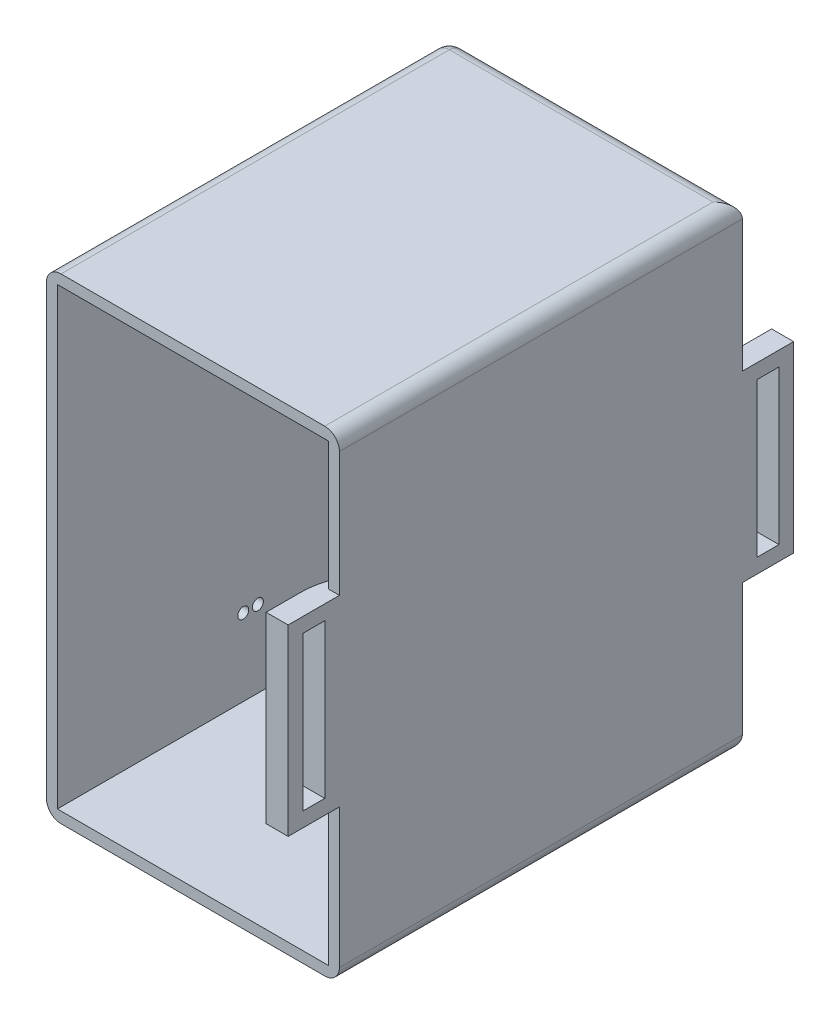
SolidWorks part; units mm, degrees
other "Markup1"
sketch "Sketch14" plane through (0, -40.2838, -28.1583) normal (-0.9752, -0.2208, -0.0136) x (-0.0916, 0.347, 0.9334)
ref_plane "Front Plane" through (0, 0, 0) normal (0, 0, 1) x (1, 0, 0)
ref_plane "Top Plane" through (0, 0, 0) normal (0, 1, 0) x (1, 0, 0)
ref_plane "Right Plane" through (0, 0, 0) normal (1, 0, 0) x (0, 0, -1)
sketch "Sketch1" plane through (0, 0, 0) normal (1, 0, 0) x (0, 0, -1)
  line L1 (-14.8417, 24.7162) -> (40.1583, 24.7162)
  line L2 (-14.8417, 24.7162) -> (-14.8417, -40.2838)
  line L3 (-14.8417, -40.2838) -> (40.1583, -40.2838)
  line L4 (40.1583, 24.7162) -> (40.1583, -40.2838)
  dimension "D1" = 65
  dimension "D2" = 55
extrude "Boss-Extrude1" add sketch "Sketch1" along normal blind 40
sketch "Sketch2" plane through (0, 0, 14.8417) normal (0, 0, 1) x (1, 0, 0)
  line L0 (0, 24.7162) -> (0, -40.2838) construction
  line L1 (38.5, -38.7838) -> (1.5, -38.7838)
  line L2 (38.5, -38.7838) -> (38.5, 23.2162)
  line L3 (38.5, 23.2162) -> (1.5, 23.2162)
  line L4 (1.5, -38.7838) -> (1.5, 23.2162)
  line L5 (40, 24.7162) -> (0, 24.7162) construction
  line L6 (40, -40.2838) -> (0, -40.2838) construction
  line L7 (40, 24.7162) -> (40, -40.2838) construction
  dimension "D1" = 1.5
  dimension "D2" = 1.5
  dimension "D3" = 1.5
  dimension "D4" = 1.5
extrude "Cut-Extrude1" cut sketch "Sketch2" against normal blind 53.5
fillet "Fillet1" radius 2 6 edges at (20, -40.2838, -40.1583) (0, -7.7838, -40.1583) (20, 24.7162, -40.1583) (0, -40.2838, -12.6583) (40, -40.2838, -12.6583) (40, 24.7162, -12.6583)
fillet "Fillet7" radius 2 2 edges at (0.5858, 24.1304, -39.5725) (0, 24.7162, -11.6583)
sketch "Sketch16" plane through (0, 0, 0) normal (-1, 0, 0) x (0, 0, 1)
  line L0 (14.8417, 22.7162) -> (14.8417, -38.2838) construction
  circle A0 centre (-12.6583, 12.7952) radius 8.4566
  circle A1 centre (-12.6583, 1.0201) radius 11.7751
  circle A2 centre (-11.4855, -25.8908) radius 9.2432
  arc A3 (-24.3328, 2.5561) -> (-14.0506, 12.7126) centre (-12.6583, 1.0201) cw
  arc A7 (-0.8832, 1.0201) -> (-5.7366, 17.6536) centre (-31.8127, 1.0201) ccw
  arc A8 (-24.3328, 2.5561) -> (-19.4593, 17.8212) centre (20.4773, -3.3395) cw
  arc A9 (-19.4593, 17.8212) -> (-5.7366, 17.6536) centre (-12.6583, 12.7952) cw
  arc A10 (-19.4593, -30.5659) -> (-2.2423, -25.8908) centre (-11.4855, -25.8908) ccw
  arc A12 (-3.652, -6.5654) -> (-0.8832, 1.0201) centre (-12.6583, 1.0201) ccw
  arc A13 (-0.8832, 1.0201) -> (-3.652, -6.5654) centre (-12.6583, 1.0201) cw
  arc A14 (-19.4593, -30.5659) -> (-20.5658, -19.3216) centre (-5.1112, -23.4774) cw
  arc A15 (-24.3328, 2.5561) -> (-22.0776, -7.3213) centre (-11.514, 0.2867) ccw
  arc A16 (-22.0776, -7.3213) -> (-20.5658, -19.3216) centre (-30.6939, -14.5022) cw
  arc A17 (-2.6448, -28.5889) -> (-3.652, -18.1251) centre (-17.2967, -24.7188) ccw
  arc A18 (-0.8832, 1.0201) -> (-2.6448, -7.3213) centre (-14.2365, -0.5165) cw
  arc A19 (-2.6448, -7.3213) -> (-3.652, -18.1251) centre (4.2202, -13.4102) ccw
  point P30 (0, 0)
  dimension "D1" = 27.5
extrude "Boss-Extrude2" add sketch "Sketch16" along normal blind 2 contours A1 A15 A0 | A8 A1 A0 | A8 A0 A1 A7 | A1 A7 A0 | A0 A1 | A1 A15 A16 A14 A2 | A14 A2 region at (0, 15.7796, -12.6449) region at (0, 9.6842, -3.0091) region at (0, 9.663, -22.0943) region at (0, -13.7186, -12.2096) region at (0, -1.1267, -12.6583) region at (0, 8.7187, -12.6583) region at (0, -25.8893, -11.4825)
sketch "Sketch17" plane through (-2, 0, 0) normal (-1, 0, 0) x (0, 0, 1)
  circle A0 centre (-15.4495, 14.2974) radius 0.75
  circle A1 centre (-13.4495, 14.2974) radius 0.75
  circle A2 centre (-4.2293, 6.2284) radius 0.75
  circle A3 centre (-6.2293, 6.2284) radius 0.75
  circle A4 centre (-20.261, -0.6295) radius 0.75
  circle A5 centre (-18.261, -0.6295) radius 0.75
  circle A6 centre (-12.5307, -28.2913) radius 0.75
  circle A7 centre (-10.5307, -28.2913) radius 0.75
  point P16 (0, 0)
  point P17 (0, 0)
  point P18 (0, 0)
  dimension "D1" = 1.5
  dimension "D2" = 1.5
  dimension "D3" = 1.5
  dimension "D4" = 1.5
  dimension "D5" = 1.5
  dimension "D6" = 1.5
  dimension "D7" = 1.5
  dimension "D8" = 2
  dimension "D9" = 2
  dimension "D10" = 2
  dimension "C" = 1.5
  dimension "D" = 2
extrude "Cut-Extrude3" cut sketch "Sketch17" against normal up to surface (3.5 mm away) up to face at (1.5, -7.7838, -11.9083)
sketch "Sketch18" plane through (0, 0, -40.1583) normal (0, 0, -1) x (-1, 0, 0)
  line L0 (-40, -38.2838) -> (-40, 22.7162) construction
  line L1 (-40, 4.7162) -> (-37, 4.7162)
  line L2 (-40, 4.7162) -> (-40, -20.2838)
  line L3 (-40, -20.2838) -> (-37, -20.2838)
  line L4 (-37, 4.7162) -> (-37, -20.2838)
  line L6 (-2, 22.7162) -> (-40, 22.7162) construction
  dimension "D1" = 25
  dimension "D2" = 18
  dimension "D3" = 3
extrude "Boss-Extrude3" add sketch "Sketch18" along normal blind 7
sketch "Sketch19" plane through (0, 0, 14.8417) normal (0, 0, 1) x (1, 0, 0)
  line L0 (40, 22.7162) -> (40, -38.2838) construction
  line L1 (40, 5.7162) -> (37, 5.7162)
  line L2 (40, 5.7162) -> (40, -19.2838)
  line L3 (40, -19.2838) -> (37, -19.2838)
  line L4 (37, 5.7162) -> (37, -19.2838)
  line L5 (38, 24.7162) -> (2, 24.7162) construction
  line L6 (38, -40.2838) -> (2, -40.2838) construction
  line L7 (38.5, 23.2162) -> (1.5, 23.2162) construction
  line L8 (1.5, -38.7838) -> (38.5, -38.7838) construction
  line L9 (0, 22.7162) -> (0, -38.2838) construction
  line L10 (1.5, 23.2162) -> (1.5, -38.7838) construction
  line L11 (38.5, -38.7838) -> (38.5, 23.2162) construction
  dimension "D1" = 19
  dimension "D2" = 3
  dimension "D3" = 25
  dimension "D4" = 65
  dimension "D5" = 62
  dimension "D6" = 40
  dimension "D7" = 37
extrude "Boss-Extrude4" add sketch "Sketch19" along normal blind 7
sketch "Sketch22" plane through (38.5, 0, 0) normal (-1, 0, 0) x (0, 0, 1)
  line L0 (14.8417, -19.2838) -> (14.8417, 5.7162) construction
  line L1 (14.8417, 5.7162) -> (11.8417, 5.7162)
  line L2 (14.8417, 5.7162) -> (14.8417, -19.2838)
  line L3 (14.8417, -19.2838) -> (11.8417, -19.2838)
  line L4 (11.8417, 5.7162) -> (11.8417, -19.2838)
  line L5 (21.8417, 5.7162) -> (14.8417, 5.7162) construction
  dimension "D1" = 0
  dimension "D2" = 25
  dimension "D3" = 3
extrude "Boss-Extrude5" add sketch "Sketch22" along normal up to surface (1.5 mm away) up to face at (37, -6.7838, 18.3417)
sketch "Sketch23" plane through (37, 0, 0) normal (-1, 0, 0) x (0, 0, 1)
  line L0 (-47.1583, 4.7162) -> (-40.1583, 4.7162) construction
  line L1 (-45.1583, 2.7162) -> (-42.1583, 2.7162)
  line L2 (-45.1583, 2.7162) -> (-45.1583, -18.2838)
  line L3 (-45.1583, -18.2838) -> (-42.1583, -18.2838)
  line L4 (-42.1583, 2.7162) -> (-42.1583, -18.2838)
  line L5 (16.8417, 3.7162) -> (19.8417, 3.7162)
  line L6 (16.8417, 3.7162) -> (16.8417, -17.2838)
  line L7 (16.8417, -17.2838) -> (19.8417, -17.2838)
  line L8 (19.8417, 3.7162) -> (19.8417, -17.2838)
  line L9 (21.8417, 5.7162) -> (11.8417, 5.7162) construction
  line L10 (-47.1583, -20.2838) -> (-40.1583, -20.2838) construction
  line L11 (21.8417, -19.2838) -> (11.8417, -19.2838) construction
  line L12 (21.8417, 5.7162) -> (21.8417, -19.2838) construction
  line L13 (14.8417, 22.7162) -> (14.8417, -38.2838) construction
  line L14 (-40.1583, -20.2838) -> (-40.1583, 4.7162) construction
  line L15 (-47.1583, -20.2838) -> (-47.1583, 4.7162) construction
  point P10 (-43.6583, 4.7162)
  point P15 (-43.6583, -20.2838)
  dimension "D1" = 2
  dimension "D2" = 2
  dimension "D3" = 2
  dimension "D4" = 2
  dimension "D5" = 2
  dimension "D6" = 2
  dimension "D7" = 2
  dimension "D8" = 2
extrude "Cut-Extrude4" cut sketch "Sketch23" against normal up to surface (3 mm away) up to face at (40, -7.4505, -12.6583)
fillet "Fillet9" radius 10 1 edges at (37, -6.7838, 11.8417)
sketch "Sketch24" plane through (0, -40.2838, 0) normal (0, -1, 0) x (1, 0, 0)
  line L0 (38, 14.8417) -> (2, 14.8417) construction
  line L1 (35.5, -2.6583) -> (38.5, -2.6583)
  line L2 (35.5, -2.6583) -> (35.5, -22.6583)
  line L3 (35.5, -22.6583) -> (38.5, -22.6583)
  line L4 (38.5, -2.6583) -> (38.5, -22.6583)
  line L5 (40, 14.8417) -> (40, -40.1583) construction
  dimension "D1" = 20
  dimension "D2" = 3
  dimension "D3" = 17.5
  dimension "D4" = 1.5
extrude "Cut-Extrude5" cut sketch "Sketch24" against normal blind 5
